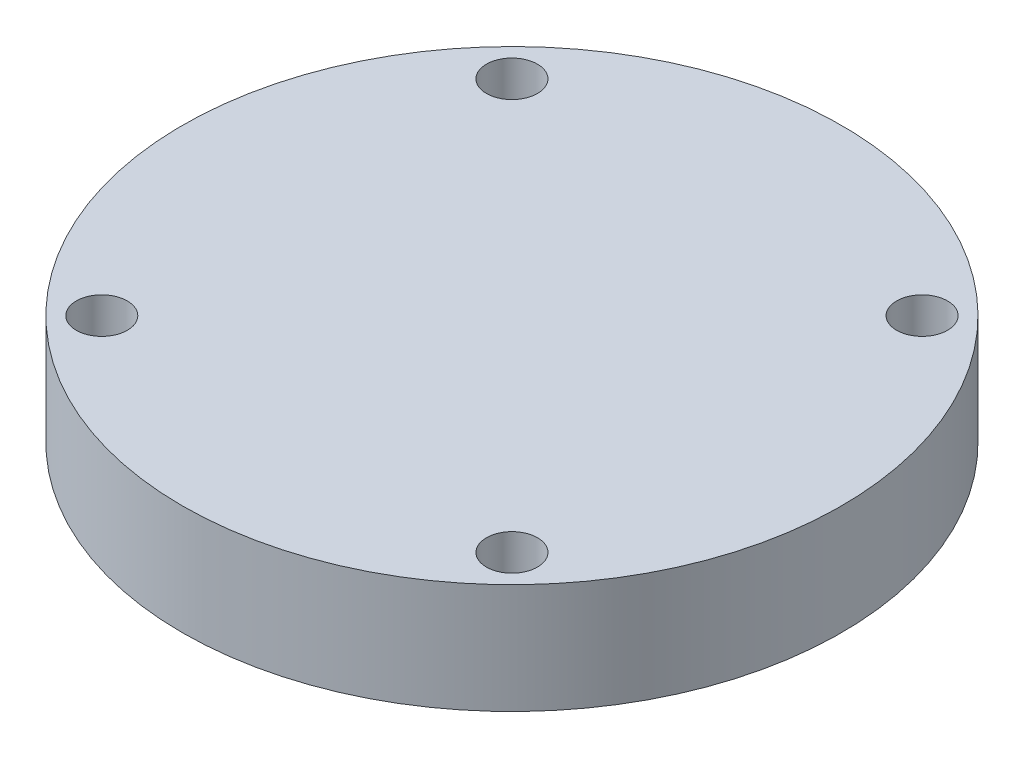
SolidWorks part; units mm, degrees
material "Copper"
ref_plane "Front Plane" through (0, 0, 0) normal (0, 0, 1) x (1, 0, 0)
ref_plane "Top Plane" through (0, 0, 0) normal (0, 1, 0) x (1, 0, 0)
ref_plane "Right Plane" through (0, 0, 0) normal (1, 0, 0) x (0, 0, -1)
ref_axis "Y Axis" through (0, 6.6675, 0) along (0, -1, 0)
sketch "outer" plane through (0, 0, 0) normal (0, 1, 0) x (1, 0, 0)
  circle A0 centre (0, 0) radius 19.05
  dimension "D1" = 38.1
extrude "Body" add sketch "outer" along normal blind 6.35
sketch "inner" plane through (0, 0, 0) normal (0, 1, 0) x (1, 0, 0)
  circle A0 centre (0, 0) radius 11.938
  dimension "D1" = 23.876
extrude "Pocket" cut sketch "inner" along normal blind 3.81
sketch "Screw Position" plane through (0, 0, 0) normal (0, 1, 0) x (1, 0, 0)
  point P0 (-11.8539, 11.8539)
  dimension "D1" = 16.764
hole_wizard "#4 Clearance Hole1" positions "Sketch7" profile "Sketch8" hole size "#4" standard "ANSI Inch" end condition through all
sketch "Sketch7" plane through (0, 6.35, 0) normal (0, 1, 0) x (1, 0, 0)
  point P0 (-11.8539, 11.8539)
sketch "Sketch8" plane through (-11.8539, 6.35, -11.8539) normal (1, 0, 0) x (0, 0, 1)
  line L0 (0, 0) -> (0, 6.35)
  line L1 (0, 6.35) -> (1.4732, 6.35)
  line L2 (1.4732, 6.35) -> (1.4732, 0)
  line L5 (1.4732, 0) -> (0, 0)
  line L11 (0, -6.35) -> (0, 107.95) construction
  dimension "Thru Hole Dia." = 2.9464
  dimension "Thru Hole Depth" = 6.35
pattern_circular "Screw Holes" count 4 over 360 about axis through (0, 6.6675, 0) along (0, -1, 0) of "#4 Clearance Hole1"
sketch "Post Sketch" plane through (0, 0, 0) normal (0, 1, 0) x (1, 0, 0)
  circle A0 centre (0, -5.334) radius 1
  circle A1 centre (5.334, -5.334) radius 1
  point P0 (0, -5.334)
  point P1 (5.334, -5.334)
  dimension "D3" = 2
  dimension "D4" = 2
  dimension "D1" = 5.334
  dimension "D2" = 7.5434
extrude "Post" add sketch "Post Sketch" against normal blind 4.572 from surface starting at face at (0, 3.81, 11.938)
pattern_circular "CirPattern1" count 4 over 360 about axis through (0, 6.6675, 0) along (0, -1, 0) of "Post"
equation "\"outer_d\"= 3 / 2in"
equation "\"top_h\"= 1 / 4in"
equation "\"screw_r\"= 0.66in"
equation "\"inner_d\"= 0.94in"
equation "\"inner_h\"= 150mil"
equation "\"D1@outer\" = \"outer_d\""
equation "\"D1@Body\" = \"top_h\""
equation "\"D1@inner\"=\"inner_d\""
equation "\"D1@Pocket\" = \"inner_h\""
equation "\"D1@Screw Position\"=\"screw_r\""
equation "\"post_r1\" = 0.21in"
equation "\"post_r2\"= \"post_r1\" * sqr ( 2 )"
equation "\"post_bottom_h\"= 0.03in"
equation "\"D1@Post Sketch\" = \"post_r1\""
equation "\"D2@Post Sketch\" = \"post_r2\""
equation "\"post_d\"= 2mm"
equation "\"D3@Post Sketch\"=\"post_d\""
equation "\"D4@Post Sketch\"=\"post_d\""
equation "\"D1@Post\" = \"inner_h\" + \"post_bottom_h\""
